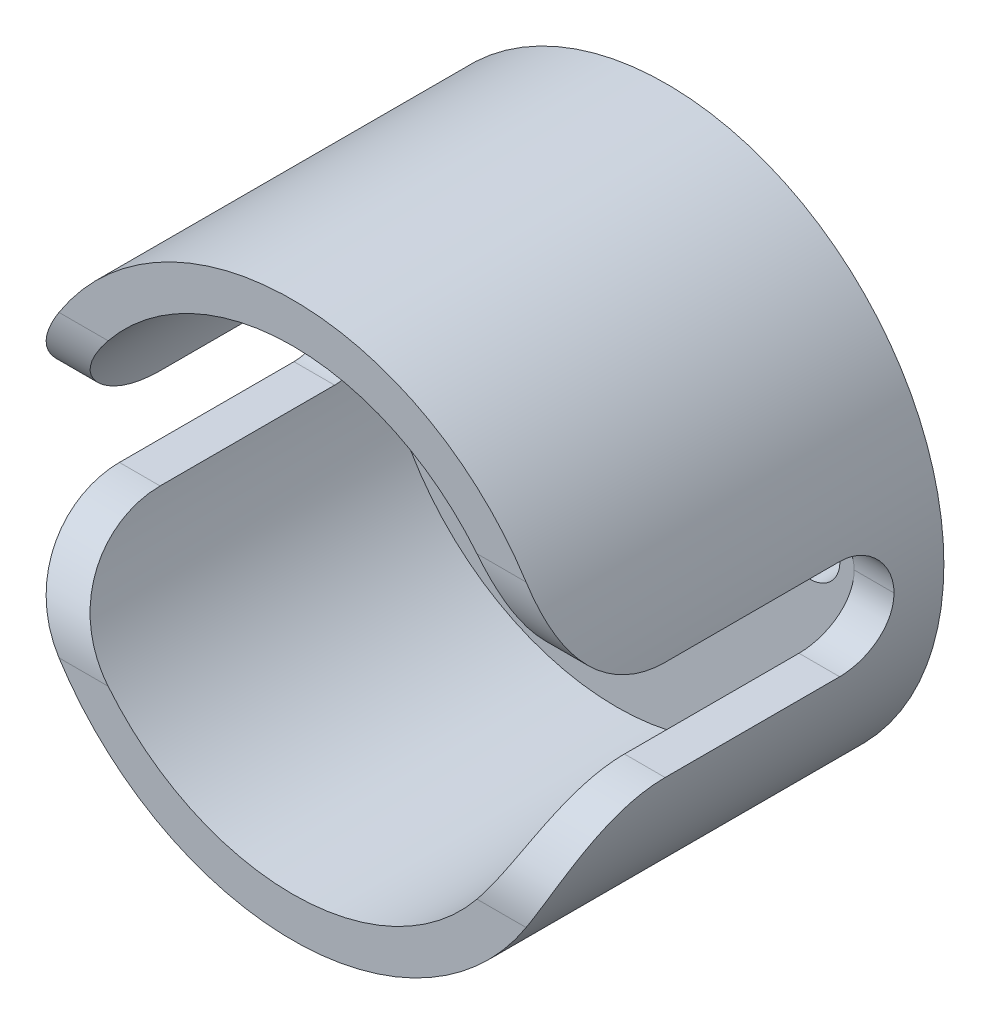
SolidWorks part; units mm, degrees
ref_plane "Front Plane" through (0, 0, 0) normal (0, 0, 1) x (1, 0, 0)
ref_plane "Top Plane" through (0, 0, 0) normal (0, 1, 0) x (1, 0, 0)
ref_plane "Right Plane" through (0, 0, 0) normal (1, 0, 0) x (0, 0, -1)
sketch "Sketch1" plane through (0, 0, 0) normal (0, 0, 1) x (1, 0, 0)
  circle A0 centre (0, 0) radius 11.125
  dimension "D1" = 22.25
extrude "Boss-Extrude1" add sketch "Sketch1" along normal blind 15
sketch "Sketch2" plane through (0, 0, 15) normal (0, 0, 1) x (1, 0, 0)
  circle A0 centre (0, 0) radius 9.525
  dimension "D1" = 19.05
extrude "Cut-Extrude1" cut sketch "Sketch2" against normal blind 13
sketch "Sketch4" plane through (0, 0, 0) normal (1, 0, 0) x (0, 0, -1)
  line L0 (-15, 2) -> (-15, -2)
  line L1 (-15, -11.125) -> (0, -11.125) construction
  line L2 (-2, 2) -> (-15, 2)
  line L3 (-2, -2) -> (-15, -2)
  line L4 (-15, 11.125) -> (-15, -11.125) construction
  line L7 (-2, -2) -> (-2, 2)
  dimension "D1" = 9.125
  dimension "D2" = 4
  dimension "D3" = 13
extrude "Cut-Extrude7" cut sketch "Sketch4" against normal blind 13 and the other way blind 13
fillet "Fillet1" radius 2 2 edges at (-10.1282, -2, 2) (-10.1282, 2, 2)
fillet "Fillet2" radius 2 2 edges at (10.1282, 2, 2) (10.1282, -2, 2)
fillet "Fillet3" radius 4 4 edges at (-10.1282, -2, 15) (-10.1282, 2, 15) (10.1282, 2, 15) (10.1282, -2, 15)
sketch "Sketch6" plane through (0, 0, 0) normal (0, 0, -1) x (-1, 0, 0)
  line L0 (0, 0) -> (0, -5.0692) construction
  line L1 (2.0956, 0) -> (-7.7693, 0) construction
  circle A0 centre (7.747, 0) radius 1.2065
  circle A1 centre (-7.747, 0) radius 1.2065
  dimension "D1" = 2.413
  dimension "D2" = 15.494
extrude "Cut-Extrude8" cut sketch "Sketch6" against normal blind 13
sketch "Sketch8" plane through (0, 0, 0) normal (0, 0, -1) x (-1, 0, 0)
  circle A0 centre (0, 0) radius 5.75
  dimension "D1" = 11.5
extrude "Cut-Extrude9" cut sketch "Sketch8" against normal blind 13
